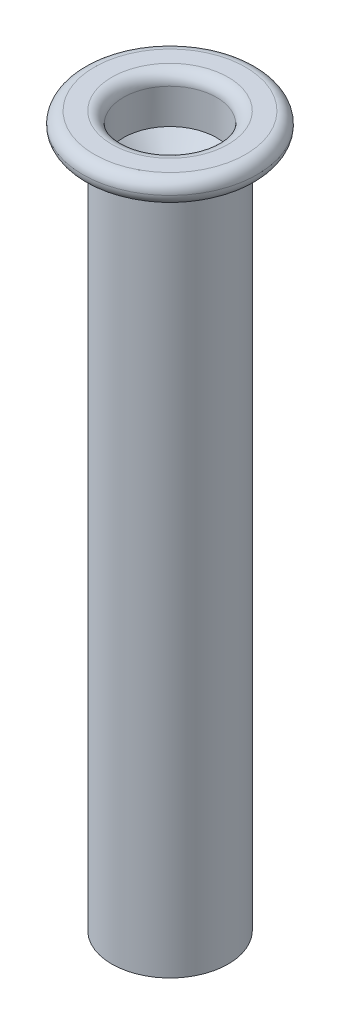
SolidWorks part; units mm, degrees
material "Cast Stainless Steel"
ref_plane "Front Plane" through (0, 0, 0) normal (0, 0, 1) x (1, 0, 0)
ref_plane "Top Plane" through (0, 0, 0) normal (0, 1, 0) x (1, 0, 0)
ref_plane "Right Plane" through (0, 0, 0) normal (1, 0, 0) x (0, 0, -1)
sketch "Sketch1" plane through (0, 0, 0) normal (0, 1, 0) x (1, 0, 0)
  circle A0 centre (0, 0) radius 2.5
  dimension "D1" = 5
extrude "Boss-Extrude1" add sketch "Sketch1" along normal blind 29.5
sketch "Sketch2" plane through (0, 29.5, 0) normal (0, 1, 0) x (1, 0, 0)
  circle A0 centre (0, 0) radius 3.75
  dimension "D1" = 7.5
extrude "Boss-Extrude2" add sketch "Sketch2" along normal blind 1
sketch "Sketch3" plane through (0, 30.5, 0) normal (0, 1, 0) x (1, 0, 0)
  circle A0 centre (0, 0) radius 2
  dimension "D1" = 4
extrude "Cut-Extrude2" cut sketch "Sketch3" against normal blind 2
sketch "Sketch4" plane through (0, 0, 0) normal (0, 0, 1) x (1, 0, 0)
  line L0 (-2, 28.5) -> (0, 26.5)
  line L1 (0, 26.5) -> (0, 28.5)
  line L2 (2, 28.5) -> (-2, 28.5) construction
  line L3 (0, 28.5) -> (-2, 28.5)
  dimension "D1" = 45
revolve "Cut-Revolve1" cut sketch "Sketch4" angle 360 about L1
fillet "Fillet1" radius 0.5 3 edges at (0, 29.5, 3.75) (0, 30.5, 2) (0, 30.5, 3.75)
